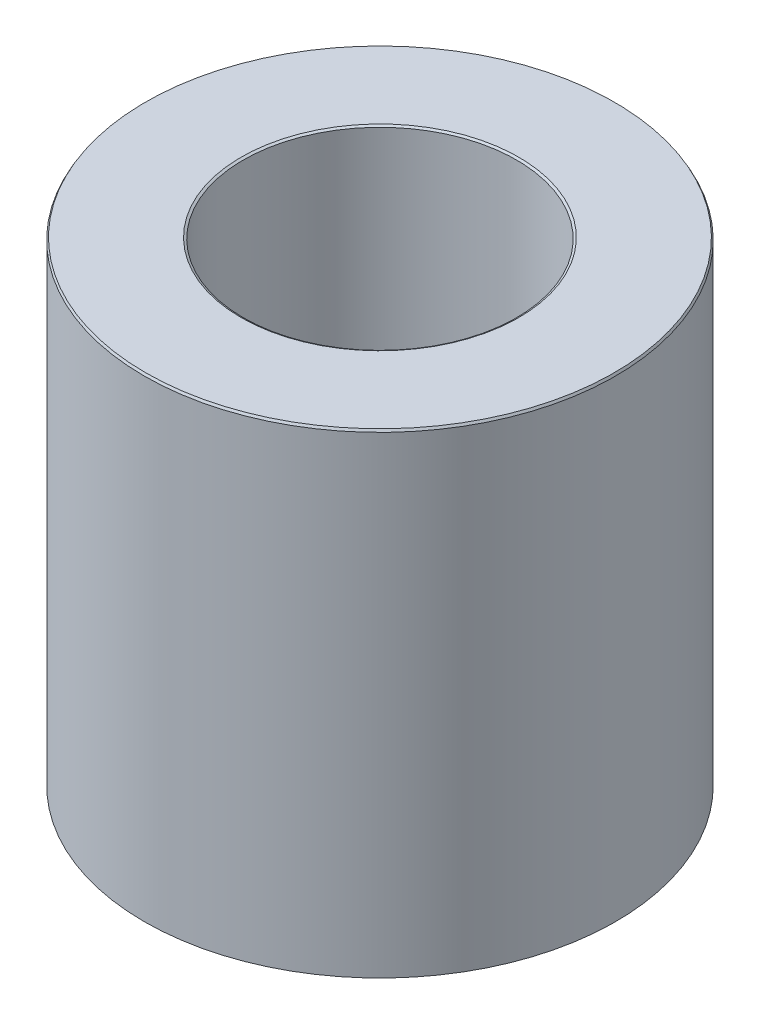
SolidWorks part; units mm, degrees
ref_plane "Front Plane" through (0, 0, 0) normal (0, 0, 1) x (1, 0, 0)
ref_plane "Top Plane" through (0, 0, 0) normal (0, 1, 0) x (1, 0, 0)
ref_plane "Right Plane" through (0, 0, 0) normal (1, 0, 0) x (0, 0, -1)
sketch "Sketch1" plane through (0, 0, 0) normal (0, 1, 0) x (1, 0, 0)
  circle A0 centre (0, 0) radius 47.5
  dimension "SLEEVE_OD" = 95
extrude "Boss-Extrude1" add sketch "Sketch1" along normal blind 95.9612
sketch "Sketch2" plane through (0, 0, 0) normal (0, 1, 0) x (1, 0, 0)
  circle A0 centre (0, 0) radius 27.5423
  dimension "BORE_D" = 55.0845
extrude "Cut-Extrude1" cut sketch "Sketch2" along normal through all
chamfer "Chamfer1" distance 0.4539 angle 29.276 4 edges at (0, 95.9612, 27.5423) (0, 0, 27.5423) (0, 0, 47.5) (0, 95.9612, 47.5) first distance on face at (0, 95.9612, 27.5423) first distance on face at (0, 0, 27.5423) first distance on face at (0, 95.9612, 47.5)
